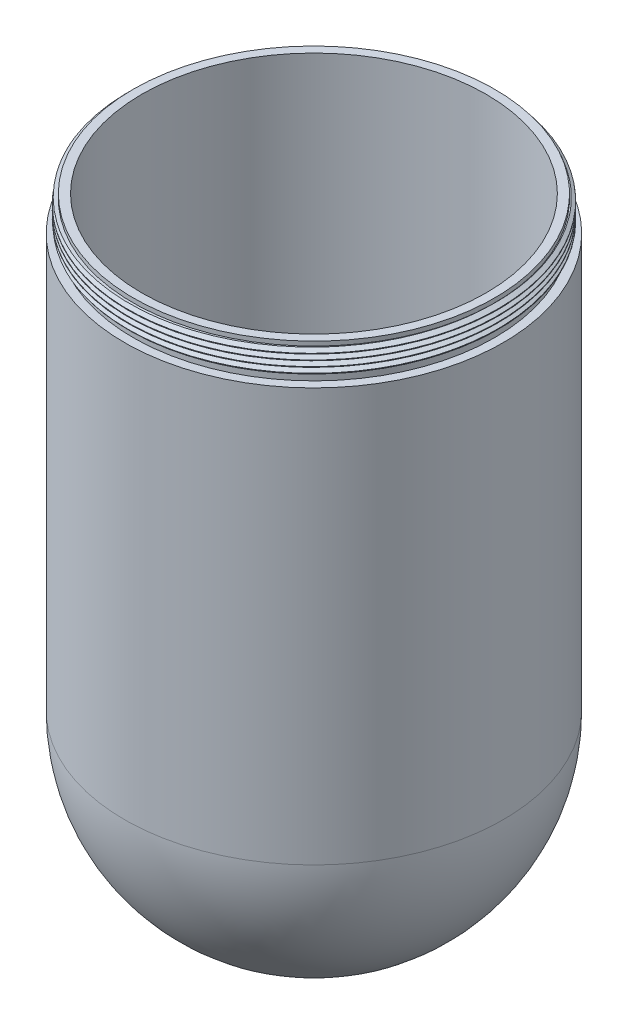
SolidWorks part; units mm, degrees
material "6061-T6 (SS)"
ref_plane "Front Plane" through (0, 0, 0) normal (0, 0, 1) x (1, 0, 0)
ref_plane "Top Plane" through (0, 0, 0) normal (0, 1, 0) x (1, 0, 0)
ref_plane "Right Plane" through (0, 0, 0) normal (1, 0, 0) x (0, 0, -1)
sketch "Sketch1" plane through (0, 0, 0) normal (0, 0, 1) x (1, 0, 0)
  line L0 (63.5, 0) -> (63.5, 152.4)
  line L1 (63.5, 152.4) -> (66.675, 152.4)
  line L2 (69.85, 152.4) -> (69.85, 0)
  line L3 (0, -63.5) -> (0, -69.85)
  line L7 (69.85, 152.4) -> (69.85, 165.1)
  line L8 (69.85, 165.1) -> (66.675, 165.1)
  line L9 (66.675, 152.4) -> (66.675, 165.1)
  arc A0 (0, -63.5) -> (63.5, 0) centre (0, 0) ccw
  arc A1 (0, -69.85) -> (69.85, 0) centre (0, 0) ccw
  dimension "D3" = 63.5
  dimension "D4" = 12.7
  dimension "D1" = 6.35
  dimension "D2" = 152.4
  dimension "D5" = 3.175
revolve "Revolve1" add sketch "Sketch1" angle 360 about L3
sketch "Sketch3" plane through (0, 165.1, 0) normal (0, 1, 0) x (1, 0, 0)
  circle A0 centre (0, 0) radius 69.85
extrude "Cut-Extrude1" cut sketch "Sketch3" against normal blind 12.7
sketch "Sketch4" plane through (0, 152.4, 0) normal (0, 1, 0) x (1, 0, 0)
  circle A0 centre (0, 0) radius 66.675
  circle A1 centre (0, 0) radius 63.5
  dimension "D1" = 3.175
extrude "Boss-Extrude2" add sketch "Sketch4" along normal blind 12.7
sketch "Sketch5" plane through (0, 165.1, 0) normal (0, 1, 0) x (1, 0, 0)
  circle A0 centre (0, 0) radius 68.2625
  circle A1 centre (0, 0) radius 66.675 construction
  circle A2 centre (0, 0) radius 66.675
  dimension "D1" = 1.5875
extrude "Boss-Extrude3" add sketch "Sketch5" against normal blind 9.525
sketch "Sketch7" plane through (0, 165.1, 0) normal (0, 1, 0) x (1, 0, 0)
  circle A0 centre (0, 0) radius 63.5
  circle A1 centre (0, 0) radius 66.675
  circle A3 centre (0, 0) radius 68.2625
  circle M2 centre (0, 0) radius 68.2625
  dimension "D1" = 3.175
extrude "Cut-Extrude2" cut sketch "Sketch7" against normal blind 1.5875 contours A1 M2
sketch "Sketch9" plane through (0, 0, 0) normal (0, 0, 1) x (1, 0, 0)
  line L0 (68.2625, 162.5867) -> (66.675, 163.518)
  line L1 (66.675, 163.518) -> (68.2625, 163.518)
  line L2 (68.2625, 162.5867) -> (68.2625, 164.4493)
  line L7 (68.2625, 164.4493) -> (66.675, 163.518)
  dimension "D2" = 1.5875
sketch "Sketch12" plane through (0, 163.5125, 0) normal (0, 1, 0) x (1, 0, 0)
  circle A0 centre (0, 0) radius 66.5736
curve "Helix/Spiral2" pitch 2.1167 height 10.5833 turns 5
sweep "Cut-Sweep4" cut profiles "Sketch9" path "Helix/Spiral2"
